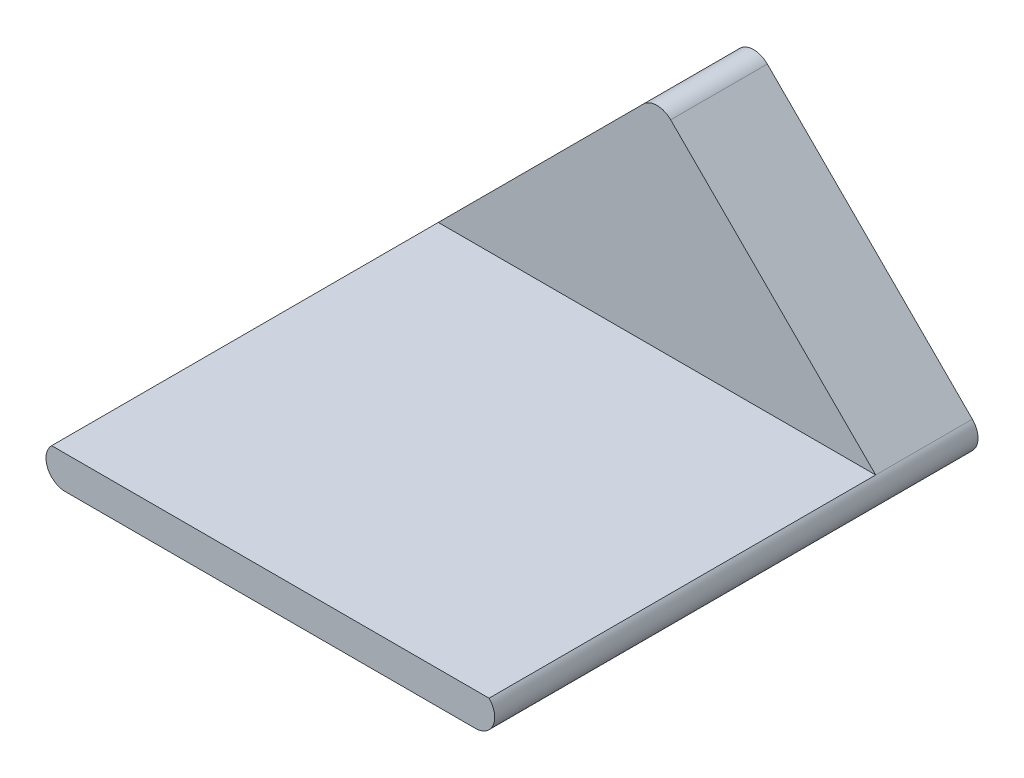
SolidWorks part; units mm, degrees
ref_plane "Front" through (0, 0, 0) normal (0, 0, 1) x (1, 0, 0)
ref_plane "Top" through (0, 0, 0) normal (0, 1, 0) x (1, 0, 0)
ref_plane "Right" through (0, 0, 0) normal (1, 0, 0) x (0, 0, -1)
sketch "Esquisse1" plane through (0, 0, 0) normal (0, 0, 1) x (1, 0, 0)
  line L0 (3.4142, 3.4142) -> (24.6274, 24.6274)
  line L1 (27.4558, 24.6274) -> (48.669, 3.4142)
  line L2 (47.2548, 0) -> (4.8284, 0)
  line L3 (3.4142, 3.4142) -> (48.669, 3.4142)
  arc A0 (48.669, 3.4142) -> (47.2548, 0) centre (47.2548, 2) cw
  arc A1 (24.6274, 24.6274) -> (27.4558, 24.6274) centre (26.0416, 23.2132) cw
  arc A2 (3.4142, 3.4142) -> (4.8284, 0) centre (4.8284, 2) ccw
  point P10 (0, 0)
  dimension "D1" = 2
  dimension "D2" = 30
extrude "Boss.-Extru.1" add sketch "Esquisse1" along normal blind 50 contours L3 A2 L2 A0 region at (26.0416, 1.7165, 0)
extrude "Boss.-Extru.2" add sketch "Esquisse1<3>" along normal blind 10 contours A1 L0 L3 L1 region at (26.0416, 10.9324, 0)
sketch "Esquisse1<3>" plane through (0, 0, 0) normal (0, 0, 1) x (1, 0, 0) same geometry as "Esquisse1"
